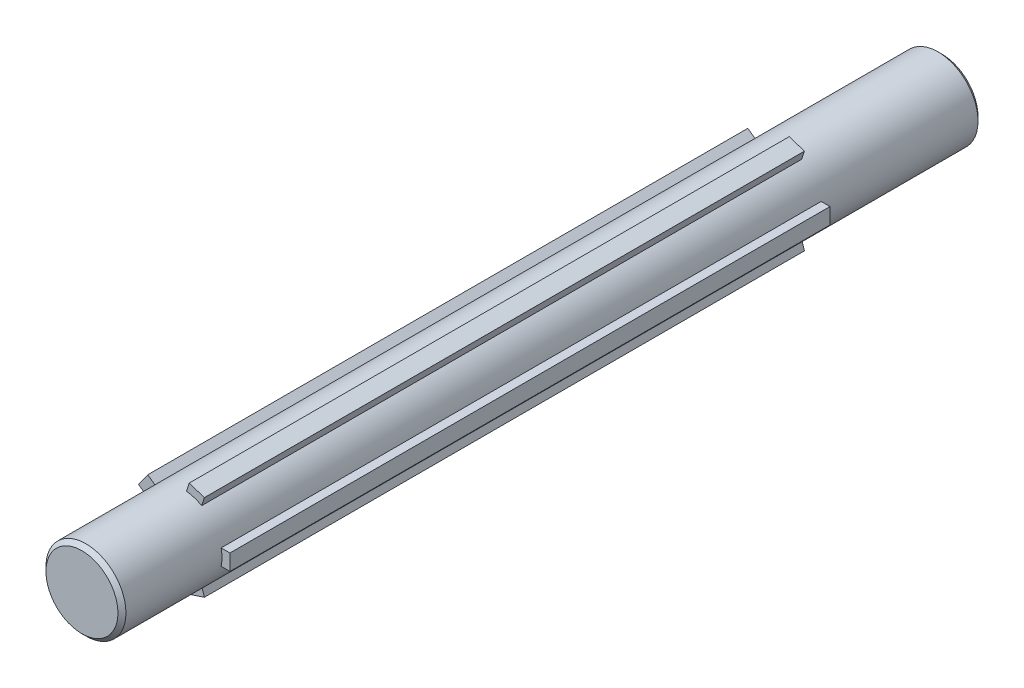
SolidWorks part; units mm, degrees
ref_plane "Front Plane" through (0, 0, 0) normal (0, 0, 1) x (1, 0, 0)
ref_plane "Top Plane" through (0, 0, 0) normal (0, 1, 0) x (1, 0, 0)
ref_plane "Right Plane" through (0, 0, 0) normal (1, 0, 0) x (0, 0, -1)
sketch "Sketch1" plane through (0, 0, 0) normal (0, 0, 1) x (1, 0, 0)
  line L0 (4.3742, -6.9904) -> (0.57, -8.2265)
  line L1 (8, 2) -> (12, 2)
  line L2 (8, 2) -> (8, -2)
  line L3 (8, -2) -> (12, -2)
  line L4 (12, 2) -> (12, -2)
  line L5 (8, 2) -> (12, -2) construction
  line L6 (8, -2) -> (12, 2) construction
  line L7 (4.3742, -6.9904) -> (5.6103, -10.7946)
  line L8 (5.6103, -10.7946) -> (1.8061, -12.0307)
  line L9 (0.57, -8.2265) -> (1.8061, -12.0307)
  line L10 (-5.2966, -6.3203) -> (-7.6477, -3.0842)
  line L11 (-5.2966, -6.3203) -> (-8.5326, -8.6715)
  line L12 (-8.5326, -8.6715) -> (-10.8838, -5.4354)
  line L13 (-7.6477, -3.0842) -> (-10.8838, -5.4354)
  line L14 (-7.6477, 3.0842) -> (-5.2966, 6.3203)
  line L15 (-7.6477, 3.0842) -> (-10.8838, 5.4354)
  line L16 (-10.8838, 5.4354) -> (-8.5326, 8.6715)
  line L17 (-5.2966, 6.3203) -> (-8.5326, 8.6715)
  line L18 (0.57, 8.2265) -> (4.3742, 6.9904)
  line L19 (0.57, 8.2265) -> (1.8061, 12.0307)
  line L20 (1.8061, 12.0307) -> (5.6103, 10.7946)
  line L21 (4.3742, 6.9904) -> (5.6103, 10.7946)
  circle A0 centre (0, 0) radius 10
  point P3 (10, 0)
  point P26 (0, 0)
  dimension "D1" = 20
  dimension "D2" = 4
  dimension "D3" = 4
  dimension "D4" = 5
extrude "Boss-Extrude1" add sketch "Sketch1" along normal blind 40 contours A0
extrude "Boss-Extrude2" add sketch "Sketch1<3>" along normal blind 150 from offset 40 contours A0 L21 L20 L19 | A0 L17 L16 L15 | A0 L13 L12 L11 | A0 L9 L8 L7 | A0 L3 L4 L1 | A0 region at (3.3886, -10.4289, 0) region at (10.9656, 0, 0) region at (-8.8713, -6.4454, 0) region at (-8.8713, 6.4454, 0) region at (3.3886, 10.4289, 0)
sketch "Sketch1<3>" plane through (0, 0, 0) normal (0, 0, 1) x (1, 0, 0) same geometry as "Sketch1"
extrude "Boss-Extrude3" add sketch "Sketch1<4>" along normal blind 25 from offset 190 contours A0
sketch "Sketch1<4>" plane through (0, 0, 0) normal (0, 0, 1) x (1, 0, 0) same geometry as "Sketch1"
chamfer "Chamfer1" distance 1 angle 45 2 edges at (10, 0, 215) (10, 0, 0)
